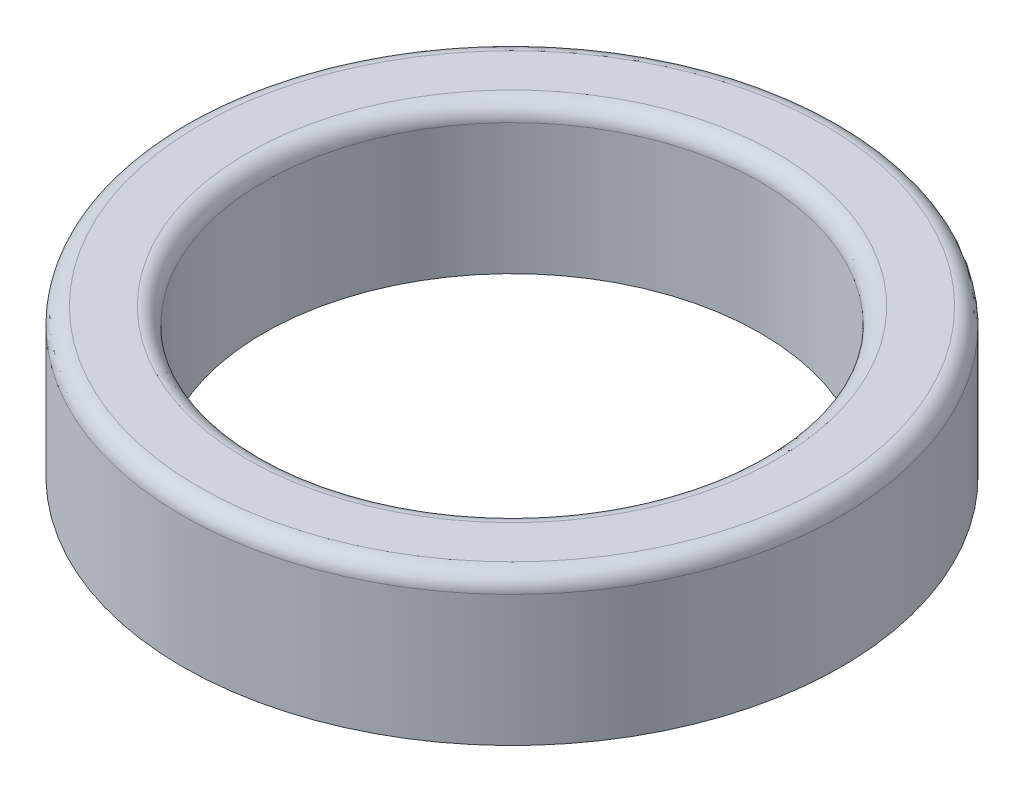
SolidWorks part; units mm, degrees
ref_plane "Front Plane" through (0, 0, 0) normal (0, 0, 1) x (1, 0, 0)
ref_plane "Top Plane" through (0, 0, 0) normal (0, 1, 0) x (1, 0, 0)
ref_plane "Right Plane" through (0, 0, 0) normal (1, 0, 0) x (0, 0, -1)
sketch "Sketch1" plane through (0, 0, 0) normal (0, 1, 0) x (1, 0, 0)
  circle A0 centre (0, 0) radius 15
  circle A1 centre (0, 0) radius 19.9
  dimension "D1" = 30
  dimension "D2" = 39.8
extrude "Boss-Extrude2" add sketch "Sketch1" along normal blind 8.9
fillet "Fillet1" radius 1 2 edges at (0, 8.9, 15) (0, 8.9, 19.9)
